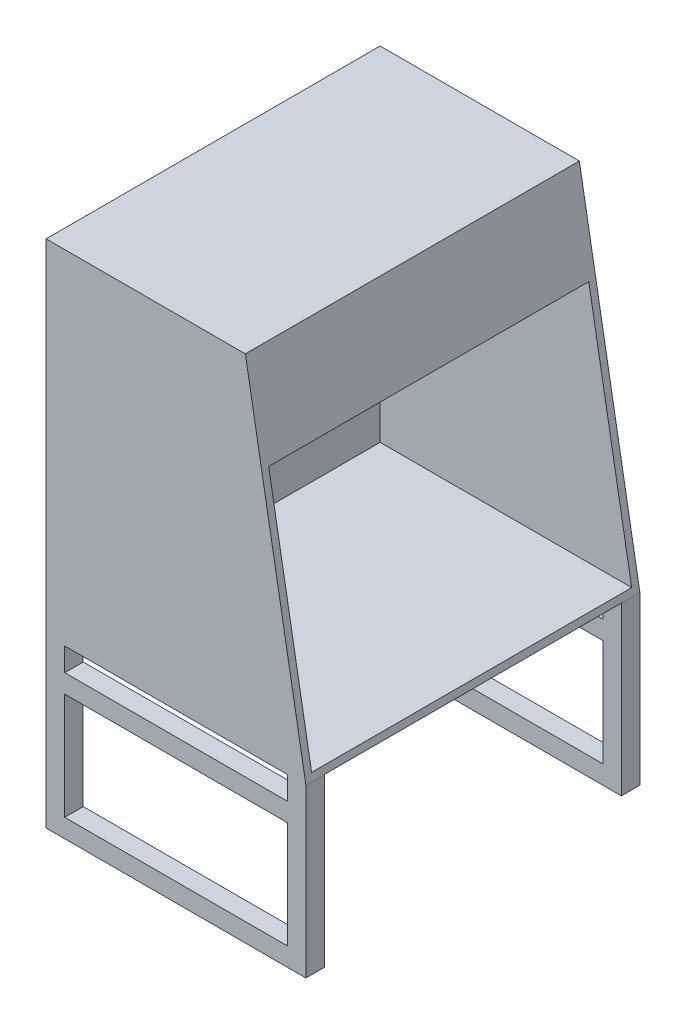
SolidWorks part; units mm, degrees
ref_plane "Front Plane" through (0, 0, 0) normal (0, 0, 1) x (1, 0, 0)
ref_plane "Top Plane" through (0, 0, 0) normal (0, 1, 0) x (1, 0, 0)
ref_plane "Right Plane" through (0, 0, 0) normal (1, 0, 0) x (0, 0, -1)
sketch "Sketch1" plane through (0, 0, 0) normal (0, 0, 1) x (1, 0, 0)
  line L1 (0, 0) -> (711.2, 0)
  line L2 (0, 0) -> (0, 939.8)
  line L5 (711.2, 0) -> (545.4879, 939.8)
  line L6 (545.4879, 939.8) -> (0, 939.8)
  dimension "D1" = 939.8
  dimension "D2" = 100
  dimension "D3" = 711.2
extrude "Boss-Extrude1" add sketch "Sketch1" along normal blind 914.4
shell "Shell1" thickness 19.05 removed face at (628.344, 469.9, 457.2)
sketch "Sketch2" plane through (19.05, 0, 0) normal (1, 0, 0) x (0, 0, -1)
  line L0 (-895.35, 685.8) -> (-19.05, 685.8)
  line L1 (-895.35, 19.05) -> (-895.35, 920.75) construction
  line L2 (-19.05, 920.75) -> (-19.05, 19.05) construction
  line L3 (-914.4, 939.8) -> (0, 939.8) construction
  line L4 (-19.05, 19.05) -> (-19.05, 920.75) construction
  line L5 (-895.35, 920.75) -> (-19.05, 920.75) construction
  line L6 (-19.05, 685.8) -> (-19.05, 920.75)
  line L7 (-895.35, 920.75) -> (-19.05, 920.75)
  line L8 (-895.35, 685.8) -> (-895.35, 920.75)
  dimension "D1" = 254
extrude "Boss-Extrude2" add sketch "Sketch2" along normal up to surface (571.225 mm away) up to face at (628.344, 469.9, 457.2)
shell "Shell2" thickness 19.05 removed face at (304.6625, 685.8, 457.2)
sketch "Sketch6" plane through (0, 0, 0) normal (0, -1, 0) x (1, 0, 0)
  line L1 (711.2, 914.4) -> (660.4, 914.4)
  line L2 (711.2, 914.4) -> (711.2, 863.6)
  line L3 (711.2, 863.6) -> (660.4, 863.6)
  line L4 (660.4, 914.4) -> (660.4, 863.6)
  line L5 (698.5, 901.7) -> (673.1, 901.7)
  line L6 (698.5, 901.7) -> (698.5, 876.3)
  line L7 (698.5, 876.3) -> (673.1, 876.3)
  line L8 (673.1, 901.7) -> (673.1, 876.3)
  line L40 (711.2, 50.8) -> (660.4, 50.8)
  line L41 (660.4, 50.8) -> (660.4, 0)
  line L42 (673.1, 38.1) -> (673.1, 12.7)
  line L43 (711.2, 0) -> (660.4, 0)
  line L44 (698.5, 12.7) -> (673.1, 12.7)
  line L45 (711.2, 50.8) -> (711.2, 0)
  line L46 (698.5, 38.1) -> (673.1, 38.1)
  line L47 (698.5, 38.1) -> (698.5, 12.7)
  line L48 (38.1, 876.3) -> (12.7, 876.3)
  line L49 (50.8, 914.4) -> (50.8, 863.6)
  line L50 (0, 914.4) -> (0, 863.6)
  line L51 (50.8, 914.4) -> (0, 914.4)
  line L52 (38.1, 901.7) -> (12.7, 901.7)
  line L53 (38.1, 901.7) -> (38.1, 876.3)
  line L54 (12.7, 901.7) -> (12.7, 876.3)
  line L55 (50.8, 863.6) -> (0, 863.6)
  line L56 (38.1, 12.7) -> (12.7, 12.7)
  line L57 (50.8, 50.8) -> (0, 50.8)
  line L58 (50.8, 0) -> (0, 0)
  line L59 (0, 50.8) -> (0, 0)
  line L60 (38.1, 38.1) -> (12.7, 38.1)
  line L61 (12.7, 38.1) -> (12.7, 12.7)
  line L62 (50.8, 50.8) -> (50.8, 0)
  line L63 (38.1, 38.1) -> (38.1, 12.7)
  line M10 (0, 0) -> (711.2, 0)
  line M11 (711.2, 0) -> (711.2, 914.4)
  line M12 (711.2, 914.4) -> (0, 914.4)
  line M13 (0, 914.4) -> (0, 0)
  dimension "D1" = 50.8
  dimension "D2" = 25.4
  dimension "D3" = 50.8
  dimension "D4" = 25.4
  dimension "D5" = 12.7
  dimension "D6" = 12.7
  dimension "D7" = 50.8
  dimension "D8" = 25.4
  dimension "D9" = 12.7
  dimension "D10" = 12.7
  dimension "D11" = 50.8
  dimension "D12" = 25.4
  dimension "D13" = 50.8
  dimension "D14" = 25.4
  dimension "D15" = 12.7
  dimension "D16" = 12.7
  dimension "D17" = 50.8
  dimension "D18" = 25.4
  dimension "D19" = 50.8
  dimension "D20" = 25.4
  dimension "D21" = 12.7
  dimension "D22" = 12.7
extrude "Boss-Extrude3" add sketch "Sketch6" along normal blind 457.2 contours L4 L3 L8 L5 L6 L7 M12 M11 | L40 L41 L46 L47 L44 L42 M10 M11 | L62 L57 L60 L63 L56 L61 M13 M10 | L55 L49 L54 L52 L53 L48 M12 M13 region at (710.4816, 0, 889) region at (50.0816, 0, 889) region at (710.4816, 0, 25.4) region at (25.4, 0, 50.0816)
sketch "Sketch7" plane through (50.8, 0, 0) normal (1, 0, 0) x (0, 0, -1)
  line L0 (-863.6, -457.2) -> (-863.6, 0) construction
  line L1 (-914.4, -457.2) -> (-863.6, -457.2)
  line L2 (-914.4, -457.2) -> (-914.4, -406.4)
  line L3 (-914.4, -406.4) -> (-863.6, -406.4)
  line L4 (-863.6, -457.2) -> (-863.6, -406.4)
  line L5 (0, -457.2) -> (0, 0) construction
  line L6 (-50.8, -457.2) -> (0, -457.2)
  line L7 (-50.8, -457.2) -> (-50.8, -406.4)
  line L8 (-50.8, -406.4) -> (0, -406.4)
  line L9 (0, -457.2) -> (0, -406.4)
  line L10 (-914.4, -457.2) -> (-914.4, 0) construction
  line L11 (-914.4, -63.5) -> (-863.6, -63.5)
  line L12 (-914.4, -63.5) -> (-914.4, -114.3)
  line L13 (-914.4, -114.3) -> (-863.6, -114.3)
  line L14 (-863.6, -63.5) -> (-863.6, -114.3)
  line L15 (-50.8, -457.2) -> (-50.8, 0) construction
  line L16 (-50.8, -63.5) -> (0, -63.5)
  line L17 (-50.8, -63.5) -> (-50.8, -114.3)
  line L18 (-50.8, -114.3) -> (0, -114.3)
  line L19 (0, -63.5) -> (0, -114.3)
  line L20 (-50.8, 0) -> (0, 0) construction
  line L21 (-914.4, 0) -> (-863.6, 0) construction
  dimension "D1" = 50.8
  dimension "D2" = 50.8
  dimension "D3" = 50.8
  dimension "D4" = 63.5
  dimension "D5" = 63.5
extrude "Boss-Extrude4" add sketch "Sketch7" along normal up to surface (609.6 mm away) up to face at (660.4, -228.6, 889)
sketch "Sketch9" plane through (19.05, 0, 0) normal (1, 0, 0) x (0, 0, -1)
  line L0 (-914.4, 0) -> (-914.4, 939.8) construction
  line L6 (-895.35, 19.05) -> (-19.05, 19.05) construction
  line L8 (-805.4, 582.05) -> (-109.4, 582.05)
  line L9 (-805.4, 582.05) -> (-805.4, 194.05)
  line L10 (-805.4, 194.05) -> (-109.4, 194.05)
  line L11 (-109.4, 582.05) -> (-109.4, 194.05)
  dimension "D1" = 388
  dimension "D2" = 696
  dimension "D3" = 109
  dimension "D4" = 175
extrude "Cut-Extrude2" cut sketch "Sketch9" against normal through all both and the other way through all
